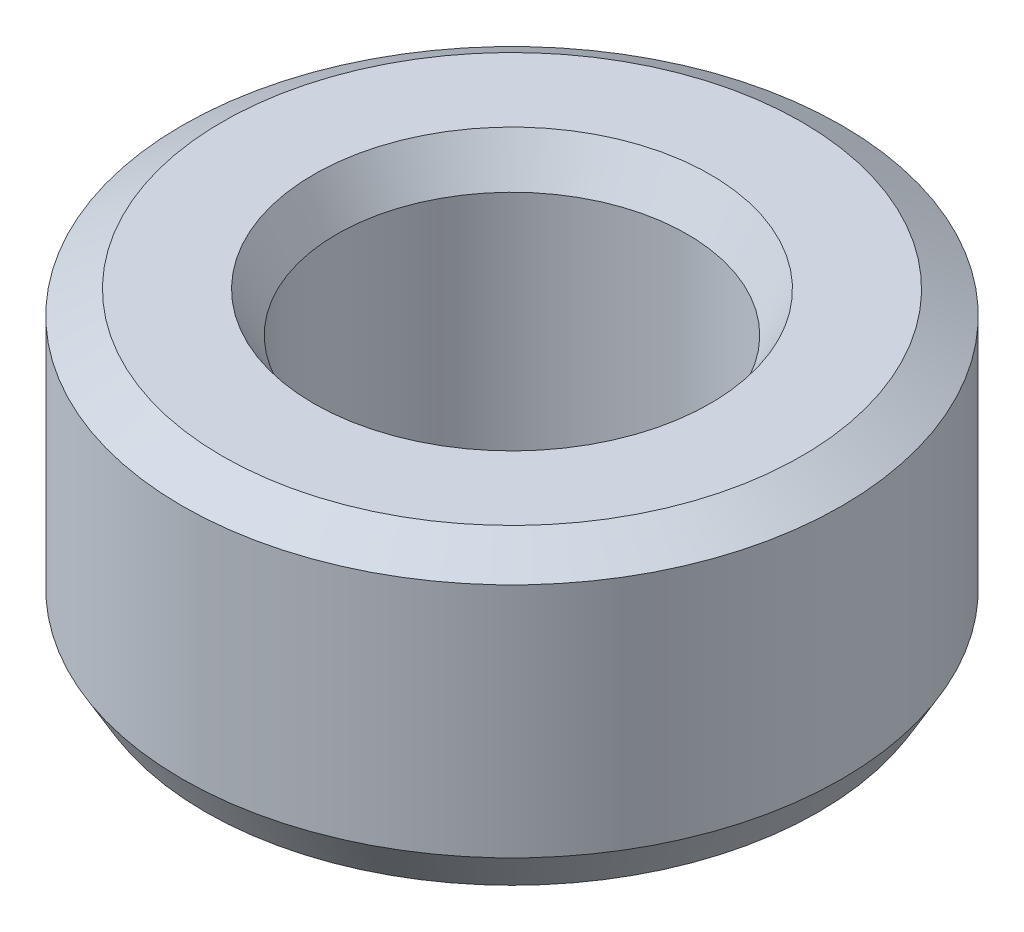
SolidWorks part; units mm, degrees
ref_plane "Front Plane" through (0, 0, 0) normal (0, 0, 1) x (1, 0, 0)
ref_plane "Top Plane" through (0, 0, 0) normal (0, 1, 0) x (1, 0, 0)
ref_plane "Right Plane" through (0, 0, 0) normal (1, 0, 0) x (0, 0, -1)
sketch "Sketch1" plane through (0, 0, 0) normal (0, 1, 0) x (1, 0, 0)
  circle A0 centre (0, 0) radius 12.5
  dimension "SLEEVE_OD" = 25
extrude "Boss-Extrude1" add sketch "Sketch1" along normal blind 11.3614
sketch "Sketch2" plane through (0, 0, 0) normal (0, 1, 0) x (1, 0, 0)
  circle A0 centre (0, 0) radius 6.6424
  dimension "BORE_D" = 13.2849
extrude "Cut-Extrude1" cut sketch "Sketch2" along normal through all
chamfer "Chamfer1" distance 0.8774 angle 60 4 edges at (0, 11.3614, 6.6424) (0, 0, 6.6424) (0, 0, 12.5) (0, 11.3614, 12.5) first distance on face at (0, 11.3614, 6.6424) first distance on face at (0, 0, 6.6424) first distance on face at (0, 11.3614, 12.5)
